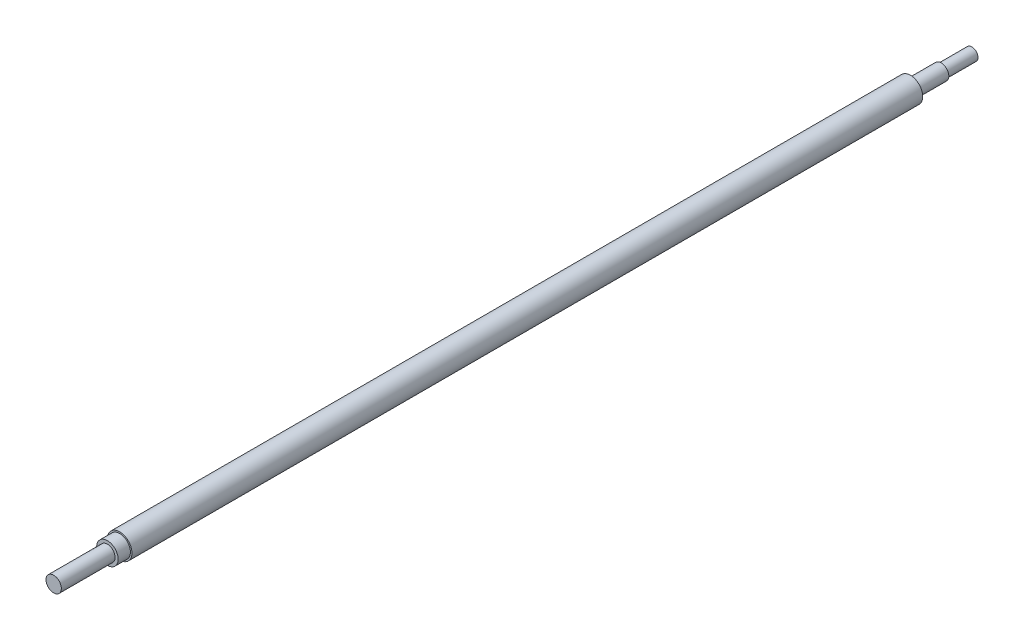
SolidWorks part; units mm, degrees
ref_plane "Piano frontale" through (0, 0, 0) normal (0, 0, 1) x (1, 0, 0)
ref_plane "Piano superiore" through (0, 0, 0) normal (0, 1, 0) x (1, 0, 0)
ref_plane "Piano destro" through (0, 0, 0) normal (1, 0, 0) x (0, 0, -1)
sketch "Schizzo2" plane through (0, 0, 0) normal (1, 0, 0) x (0, 0, -1)
  line L0 (-2, 0) -> (-2, 5)
  line L1 (-2, 5) -> (33, 5)
  line L2 (33, 5) -> (33, 7)
  line L3 (33, 7) -> (41, 7)
  line L6 (41, 7) -> (41, 8)
  line L7 (41, 8) -> (556, 8)
  line L8 (556, 8) -> (556, 5)
  line L9 (556, 5) -> (576, 5)
  line L10 (576, 5) -> (576, 4)
  line L11 (596, 0) -> (-2, 0)
  line L14 (596, 0) -> (596, 4)
  line L15 (0, 0) -> (351.0218, 0) construction
  line L18 (576, 4) -> (596, 4)
  point P33 (0, 0)
  dimension "D2" = 10
  dimension "D3" = 14
  dimension "D5" = 16
  dimension "D6" = 10
  dimension "D7" = 8
  dimension "D8" = 35
  dimension "D9" = 8
  dimension "D11" = 515
  dimension "D12" = 20
  dimension "D13" = 20
revolve "Rivoluzione2" add sketch "Schizzo2" angle 360 about L15
